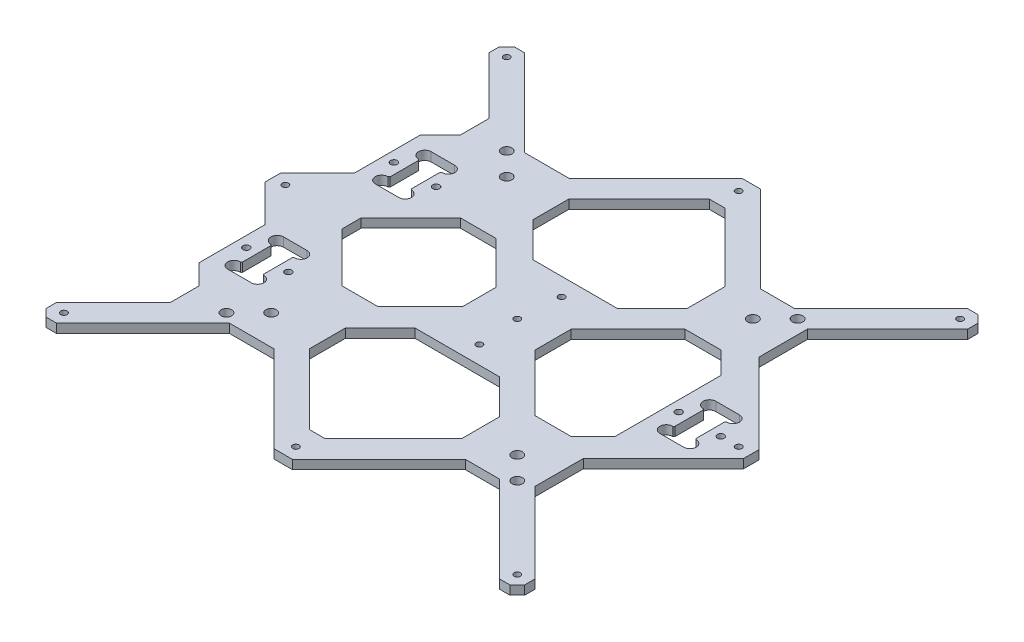
SolidWorks part; units mm, degrees
material "6063-O, Extruded Rod (SS)"
ref_plane "Front Plane" through (0, 0, 0) normal (0, 0, 1) x (1, 0, 0)
ref_plane "Top Plane" through (0, 0, 0) normal (0, 1, 0) x (1, 0, 0)
ref_plane "Right Plane" through (0, 0, 0) normal (1, 0, 0) x (0, 0, -1)
sketch "Sketch2" plane through (0, 0, 0) normal (0, 1, 0) x (1, 0, 0)
  line L0 (162, 177.023) -> (141.977, 157)
  line L1 (141.977, 157) -> (125, 157)
  line L2 (125, 157) -> (101.5, 180.5)
  line L3 (101.5, 189.5) -> (125, 213)
  line L4 (125, 213) -> (141.977, 213)
  line L5 (141.977, 213) -> (162, 192.977)
  line L6 (251.5, 210.0147) -> (240.9853, 220.5294)
  line L7 (240.9853, 220.5294) -> (224.0147, 220.5294)
  line L8 (224.0147, 220.5294) -> (197, 193.5147)
  line L9 (197, 176.4853) -> (224.0147, 149.4706)
  line L10 (224.0147, 149.4706) -> (240.9853, 149.4706)
  line L11 (240.9853, 149.4706) -> (251.5, 159.9853)
  line L12 (184.4001, 296) -> (225.4001, 255)
  line L13 (225.4001, 255) -> (241.5147, 255)
  line L14 (241.5147, 255) -> (282.5147, 296)
  line L15 (282.5147, 296) -> (287.4852, 296)
  line L16 (287.4852, 296) -> (291, 292.4852)
  line L17 (291, 292.4852) -> (291, 287.5147)
  line L18 (291, 287.5147) -> (253, 249.5147)
  line L19 (253, 249.5147) -> (253, 226.667)
  line L20 (253, 226.667) -> (291, 188.667)
  line L21 (291, 188.667) -> (291, 181.333)
  line L22 (291, 181.333) -> (253, 143.333)
  line L23 (253, 143.333) -> (253, 120.4853)
  line L24 (253, 120.4853) -> (291, 82.4853)
  line L25 (291, 82.4853) -> (291, 77.5148)
  line L26 (291, 77.5148) -> (287.4852, 74)
  line L27 (287.4852, 74) -> (282.5147, 74)
  line L28 (282.5147, 74) -> (241.5147, 115)
  line L29 (241.5147, 115) -> (225.4001, 115)
  line L30 (225.4001, 115) -> (184.4001, 74)
  line L31 (184.4001, 74) -> (175.5999, 74)
  line L32 (175.5999, 74) -> (134.5999, 115)
  line L33 (134.5999, 115) -> (113.4853, 115)
  line L34 (113.4853, 115) -> (72.4853, 74)
  line L35 (72.4853, 74) -> (67.5148, 74)
  line L36 (67.5148, 74) -> (64, 77.5148)
  line L37 (64, 77.5148) -> (64, 82.4853)
  line L38 (64, 82.4853) -> (91, 109.4853)
  line L39 (91, 109.4853) -> (91, 123)
  line L40 (91, 123) -> (81.5, 132.5)
  line L41 (81.5, 132.5) -> (81.5, 163.7609)
  line L42 (81.5, 163.7609) -> (64, 181.2609)
  line L43 (64, 188.7391) -> (81.5, 206.2391)
  line L44 (81.5, 206.2391) -> (81.5, 237.5)
  line L45 (81.5, 237.5) -> (91, 247)
  line L46 (91, 247) -> (91, 260.5147)
  line L47 (91, 260.5147) -> (64, 287.5147)
  line L48 (64, 287.5147) -> (64, 292.4852)
  line L49 (64, 292.4852) -> (67.5148, 296)
  line L50 (67.5148, 296) -> (72.4853, 296)
  line L51 (72.4853, 296) -> (113.4853, 255)
  line L52 (113.4853, 255) -> (134.5999, 255)
  line L53 (134.5999, 255) -> (175.5999, 296)
  line L54 (175.5999, 296) -> (184.4001, 296)
  line L55 (143, 246.4158) -> (143, 229.5663)
  line L56 (143, 229.5663) -> (159.5663, 213)
  line L57 (159.5663, 213) -> (199.5147, 213)
  line L58 (199.5147, 213) -> (216, 229.4853)
  line L59 (216, 229.4853) -> (216, 247.4296)
  line L60 (216, 247.4296) -> (183.6826, 279.747)
  line L61 (183.6826, 279.747) -> (176.3174, 279.7332)
  line L62 (176.3174, 279.7332) -> (143, 246.4158)
  line L63 (143, 123.5842) -> (143, 140.4337)
  line L64 (143, 140.4337) -> (159.5663, 157)
  line L65 (159.5663, 157) -> (199.5147, 157)
  line L66 (199.5147, 157) -> (216, 140.5147)
  line L67 (216, 140.5147) -> (216, 122.5704)
  line L68 (216, 122.5704) -> (183.6826, 90.253)
  line L69 (183.6826, 90.253) -> (176.3174, 90.2668)
  line L70 (176.3174, 90.2668) -> (143, 123.5842)
  line L71 (101.5, 226.75) -> (101.5, 213.25)
  line L72 (271.5, 191.75) -> (271.5, 178.25)
  line L73 (101.5, 156.75) -> (101.5, 143.25)
  line L74 (91.5, 226.75) -> (91.5, 213.25)
  line L75 (261.5, 191.75) -> (261.5, 178.25)
  line L76 (91.5, 156.75) -> (91.5, 143.25)
  line L77 (93.6792, 358.4107) -> (93.6792, 347.8262)
  line L78 (93.6792, 347.8262) -> (93.9406, 345.7354)
  line L79 (93.9406, 345.7354) -> (94.4633, 344.2327)
  line L80 (94.4633, 344.2327) -> (95.182, 343.1873)
  line L81 (95.182, 343.1873) -> (96.1846, 341.9648)
  line L82 (96.1846, 341.9648) -> (97.8105, 341.4329)
  line L83 (97.8105, 341.4329) -> (99.6248, 341.0966)
  line L84 (99.6248, 341.0966) -> (101.977, 341.3579)
  line L85 (101.977, 341.3579) -> (104.0024, 342.4033)
  line L86 (104.0024, 342.4033) -> (105.1131, 344.2327)
  line L87 (105.1131, 344.2327) -> (105.5705, 346.7155)
  line L88 (105.5705, 346.7155) -> (105.5705, 349.1983)
  line L89 (105.5705, 349.1983) -> (105.5705, 358.4107)
  line L90 (79.8932, 349.3289) -> (80.0892, 349.3289)
  line L91 (80.0892, 349.3289) -> (81.0039, 348.8063)
  line L92 (81.0039, 348.8063) -> (82.0493, 347.4342)
  line L93 (82.0493, 347.4342) -> (86.4922, 341.0966)
  line L94 (73.5556, 341.1619) -> (73.5556, 358.4107)
  line L95 (73.5556, 358.4107) -> (80.6119, 358.4107)
  line L96 (80.6119, 358.4107) -> (82.768, 357.7574)
  line L97 (82.768, 357.7574) -> (83.8134, 356.7773)
  line L98 (83.8134, 356.7773) -> (84.5321, 355.4706)
  line L99 (84.5321, 355.4706) -> (84.8588, 353.7065)
  line L100 (84.8588, 353.7065) -> (84.5321, 352.0078)
  line L101 (84.5321, 352.0078) -> (83.6827, 350.5703)
  line L102 (83.6827, 350.5703) -> (82.5067, 349.8517)
  line L103 (82.5067, 349.8517) -> (81.3306, 349.525)
  line L104 (81.3306, 349.525) -> (79.8932, 349.3289)
  line L105 (79.8932, 349.3289) -> (78.1291, 349.3289)
  line L106 (78.1291, 349.3289) -> (73.5556, 349.3289)
  line L107 (113.0897, 345.4442) -> (114.2004, 343.4842)
  line L108 (114.2004, 343.4842) -> (116.6178, 341.8507)
  line L109 (116.6178, 341.8507) -> (118.9699, 341.1974)
  line L110 (118.9699, 341.1974) -> (122.4328, 341.7201)
  line L111 (122.4328, 341.7201) -> (124.0662, 343.0268)
  line L112 (124.0662, 343.0268) -> (125.2422, 345.1176)
  line L113 (125.2422, 345.1176) -> (125.2422, 346.359)
  line L114 (125.2422, 346.359) -> (124.9156, 347.4697)
  line L115 (124.9156, 347.4697) -> (123.7395, 348.7764)
  line L116 (123.7395, 348.7764) -> (122.5635, 349.2991)
  line L117 (122.5635, 349.2991) -> (116.7485, 351.0632)
  line L118 (116.7485, 351.0632) -> (115.0497, 352.1739)
  line L119 (115.0497, 352.1739) -> (114.0044, 353.4153)
  line L120 (114.0044, 353.4153) -> (113.8737, 354.5914)
  line L121 (113.8737, 354.5914) -> (114.135, 356.3554)
  line L122 (114.135, 356.3554) -> (115.3764, 357.6622)
  line L123 (115.3764, 357.6622) -> (117.4672, 358.4462)
  line L124 (117.4672, 358.4462) -> (120.0807, 358.5769)
  line L125 (120.0807, 358.5769) -> (122.8248, 357.8582)
  line L126 (122.8248, 357.8582) -> (123.9355, 356.8128)
  line L127 (123.9355, 356.8128) -> (124.3929, 355.5714)
  line L128 (130.9954, 341.0312) -> (137.9864, 358.5414)
  line L129 (137.9864, 358.5414) -> (139.0972, 358.5414)
  line L130 (139.0972, 358.5414) -> (145.9575, 341.0312)
  line L131 (143.9343, 346.1951) -> (133.0803, 346.1927)
  line L132 (55, 341.1619) -> (55, 358.4107)
  line L133 (55, 358.4107) -> (62.0563, 358.4107)
  line L134 (62.0563, 358.4107) -> (64.2125, 357.7574)
  line L135 (64.2125, 357.7574) -> (65.2578, 356.7773)
  line L136 (65.2578, 356.7773) -> (65.9765, 355.4706)
  line L137 (65.9765, 355.4706) -> (66.3032, 353.7065)
  line L138 (66.3032, 353.7065) -> (65.9765, 352.0078)
  line L139 (65.9765, 352.0078) -> (65.1272, 350.5703)
  line L140 (65.1272, 350.5703) -> (63.9511, 349.8517)
  line L141 (63.9511, 349.8517) -> (62.7751, 349.525)
  line L142 (62.7751, 349.525) -> (61.3376, 349.3289)
  line L143 (61.3376, 349.3289) -> (59.5735, 349.3289)
  line L144 (59.5735, 349.3289) -> (55, 349.3289)
  line L145 (251.5, 210.0147) -> (251.5, 159.9853)
  line L146 (197, 193.5147) -> (197, 176.4853)
  line L147 (64, 188.7391) -> (64, 181.2609)
  line L148 (101.5, 189.5) -> (101.5, 180.5)
  line L149 (162, 192.977) -> (162, 177.023)
  line L150 (102.1, 142.75) -> (102, 142.75)
  line L151 (272.1, 177.75) -> (272, 177.75)
  line L152 (102.1, 212.75) -> (102, 212.75)
  line L153 (90.9, 142.75) -> (91, 142.75)
  line L154 (260.9, 177.75) -> (261, 177.75)
  line L155 (90.9, 212.75) -> (91, 212.75)
  line L156 (102, 142.75) -> (101.5, 143.25)
  line L157 (272, 177.75) -> (271.5, 178.25)
  line L158 (102, 212.75) -> (101.5, 213.25)
  line L159 (91, 142.75) -> (91.5, 143.25)
  line L160 (261, 177.75) -> (261.5, 178.25)
  line L161 (91, 212.75) -> (91.5, 213.25)
  line L162 (102.1, 157.25) -> (102, 157.25)
  line L163 (272.1, 192.25) -> (272, 192.25)
  line L164 (102.1, 227.25) -> (102, 227.25)
  line L165 (90.9, 157.25) -> (91, 157.25)
  line L166 (260.9, 192.25) -> (261, 192.25)
  line L167 (90.9, 227.25) -> (91, 227.25)
  line L168 (101.5, 156.75) -> (102, 157.25)
  line L169 (271.5, 191.75) -> (272, 192.25)
  line L170 (101.5, 226.75) -> (102, 227.25)
  line L171 (91.5, 156.75) -> (91, 157.25)
  line L172 (261.5, 191.75) -> (261, 192.25)
  line L173 (91.5, 226.75) -> (91, 227.25)
  line L174 (90.9, 163.25) -> (102.1, 163.25)
  line L175 (260.9, 198.25) -> (272.1, 198.25)
  line L176 (90.9, 233.25) -> (102.1, 233.25)
  line L177 (90.9, 136.75) -> (102.1, 136.75)
  line L178 (260.9, 171.75) -> (272.1, 171.75)
  line L179 (90.9, 206.75) -> (102.1, 206.75)
  arc A0 (102.1, 206.75) -> (102.1, 212.75) centre (102.1, 209.75) ccw
  arc A1 (272.1, 171.75) -> (272.1, 177.75) centre (272.1, 174.75) ccw
  arc A2 (102.1, 136.75) -> (102.1, 142.75) centre (102.1, 139.75) ccw
  arc A3 (90.9, 142.75) -> (90.9, 136.75) centre (90.9, 139.75) ccw
  arc A4 (90.9, 212.75) -> (90.9, 206.75) centre (90.9, 209.75) ccw
  arc A5 (260.9, 177.75) -> (260.9, 171.75) centre (260.9, 174.75) ccw
  arc A6 (102.1, 157.25) -> (102.1, 163.25) centre (102.1, 160.25) ccw
  arc A7 (102.1, 227.25) -> (102.1, 233.25) centre (102.1, 230.25) ccw
  arc A8 (272.1, 192.25) -> (272.1, 198.25) centre (272.1, 195.25) ccw
  arc A9 (90.9, 163.25) -> (90.9, 157.25) centre (90.9, 160.25) ccw
  arc A10 (260.9, 198.25) -> (260.9, 192.25) centre (260.9, 195.25) ccw
  arc A11 (90.9, 233.25) -> (90.9, 227.25) centre (90.9, 230.25) ccw
  circle A12 centre (318.6, 4.9) radius 2.55
  circle A13 centre (318.6, 28.1) radius 2.55
  circle A14 centre (295.4, 28.1) radius 2.55
  circle A15 centre (295.4, 4.9) radius 2.55
  circle A16 centre (281.6, 4.9) radius 2.55
  circle A17 centre (258.4, 4.9) radius 2.55
  circle A18 centre (258.4, 28.1) radius 2.55
  circle A19 centre (281.6, 28.1) radius 2.55
  circle A20 centre (111.6, 4.9) radius 2.55
  circle A21 centre (111.6, 28.1) radius 2.55
  circle A22 centre (88.4, 28.1) radius 2.55
  circle A23 centre (88.4, 4.9) radius 2.55
  circle A24 centre (74.6, 4.9) radius 2.55
  circle A25 centre (74.6, 28.1) radius 2.55
  circle A26 centre (51.4, 28.1) radius 2.55
  circle A27 centre (51.4, 4.9) radius 2.55
  circle A28 centre (360, 39.8) radius 1.5
  circle A29 centre (10, 39.8) radius 1.5
  circle A30 centre (340, 359.8) radius 1.5
  circle A31 centre (30, 39.8) radius 1.5
  circle A32 centre (42.9, 67.8) radius 1.5
  circle A33 centre (340, 39.8) radius 1.5
  circle A34 centre (10, 359.8) radius 1.5
  circle A35 centre (350, 19.8) radius 1.5
  circle A36 centre (47, 99.8) radius 1.5
  circle A37 centre (3.7, 181.1) radius 1.5
  circle A38 centre (20, 19.8) radius 1.5
  circle A39 centre (4.9, 67.8) radius 1.5
  circle A40 centre (360, 359.8) radius 1.5
  circle A41 centre (42.9, 161.8) radius 1.5
  circle A42 centre (3.7, 99.8) radius 1.5
  circle A43 centre (30, 359.8) radius 1.5
  circle A44 centre (47, 174.7) radius 1.5
  circle A45 centre (4.9, 161.8) radius 1.5
  circle A46 centre (46.5, 269.3) radius 1.5
  circle A47 centre (15, 247.8) radius 1.5
  circle A48 centre (3.5, 269.3) radius 1.5
  circle A49 centre (15, 290.8) radius 1.5
  circle A50 centre (180, 80) radius 1.5
  circle A51 centre (180, 290) radius 1.5
  circle A52 centre (285, 80) radius 1.5
  circle A53 centre (70, 290) radius 1.5
  circle A54 centre (285, 290) radius 1.5
  circle A55 centre (70, 185) radius 1.5
  circle A56 centre (180, 185) radius 1.5
  circle A57 centre (285, 185) radius 1.5
  circle A58 centre (256.5, 185) radius 1.6
  circle A59 centre (276.5, 185) radius 1.6
  circle A60 centre (106.5, 220) radius 1.6
  circle A61 centre (106.5, 150) radius 1.6
  circle A62 centre (86.5, 220) radius 1.6
  circle A63 centre (86.5, 150) radius 1.6
  circle A64 centre (70, 80) radius 1.5
  circle A65 centre (181.5, 165.5) radius 1.5
  circle A66 centre (181.5, 204.5) radius 1.5
  circle A67 centre (40, 7) radius 1.6
  circle A68 centre (331, 7) radius 1.6
  circle A69 centre (343, 7) radius 1.6
  circle A70 centre (120, 13) radius 1.6
  circle A71 centre (120, 4) radius 1.6
  circle A72 centre (230, 13) radius 1.6
  circle A73 centre (230, 4) radius 1.6
  circle A74 centre (333.4, 205) radius 2.1
  circle A75 centre (333.4, 88) radius 2.1
  circle A76 centre (26, 7) radius 1.6
  circle A77 centre (153, 13) radius 1.6
  circle A78 centre (153, 4) radius 1.6
  spline S0 degree 2 poles (5, 370) (2.5, 367.5) (0, 365) knots 1472.868668 1472.868668 1472.868668 1479.939736 1479.939736 1479.939736
  spline S1 degree 2 poles (365, 370) (185, 370) (5, 370) knots 1112.868668 1112.868668 1112.868668 1472.868668 1472.868668 1472.868668
  spline S2 degree 2 poles (370, 365) (367.5, 367.5) (365, 370) knots 1105.7976 1105.7976 1105.7976 1112.868668 1112.868668 1112.868668
  spline S3 degree 2 poles (370, 5) (370, 185) (370, 365) knots 745.7976 745.7976 745.7976 1105.7976 1105.7976 1105.7976
  spline S4 degree 2 poles (365, 0) (367.5, 2.5) (370, 5) knots 738.726533 738.726533 738.726533 745.7976 745.7976 745.7976
  spline S5 degree 2 poles (345, 0) (355, 0) (365, 0) knots 718.726533 718.726533 718.726533 738.726533 738.726533 738.726533
  spline S6 degree 2 poles (341, 4) (343, 2) (345, 0) knots 710.241251 710.241251 710.241251 718.726533 718.726533 718.726533
  spline S7 degree 2 poles (333, 4) (337, 4) (341, 4) knots 704.241251 704.241251 704.241251 710.241251 710.241251 710.241251
  spline S8 degree 2 poles (329, 0) (331, 2) (333, 4) knots 698.584397 698.584397 698.584397 704.241251 704.241251 704.241251
  spline S9 degree 2 poles (151, 0) (240, 0) (329, 0) knots 507.584397 507.584397 507.584397 698.584397 698.584397 698.584397
  spline S10 degree 2 poles (146, 5) (148.5, 2.5) (151, 0) knots 501.927543 501.927543 501.927543 507.584397 507.584397 507.584397
  spline S11 degree 2 poles (127, 5) (136.5, 5) (146, 5) knots 487.927543 487.927543 487.927543 501.927543 501.927543 501.927543
  spline S12 degree 2 poles (122, 0) (124.5, 2.5) (127, 5) knots 482.270688 482.270688 482.270688 487.927543 487.927543 487.927543
  spline S13 degree 2 poles (41, 0) (81.5, 0) (122, 0) knots 407.270688 407.270688 407.270688 482.270688 482.270688 482.270688
  spline S14 degree 2 poles (37, 4) (39, 2) (41, 0) knots 401.613834 401.613834 401.613834 407.270688 407.270688 407.270688
  spline S15 degree 2 poles (29, 4) (33, 4) (37, 4) knots 395.613834 395.613834 395.613834 401.613834 401.613834 401.613834
  spline S16 degree 2 poles (25, 0) (27, 2) (29, 4) knots 387.128553 387.128553 387.128553 395.613834 395.613834 395.613834
  spline S17 degree 2 poles (5, 0) (15, 0) (25, 0) knots 367.128553 367.128553 367.128553 387.128553 387.128553 387.128553
  spline S18 degree 2 poles (0, 5) (2.5, 2.5) (5, 0) knots 360.191742 360.191742 360.191742 367.128553 367.128553 367.128553
  spline S19 degree 2 poles (0, 365) (0, 185) (0, 5) knots 0 0 0 360.191742 360.191742 360.191742
  spline S20 degree 2 poles (93, 31.5) (100, 31.5) (107, 31.5) knots 1110.421356 1110.421356 1110.421356 1117.046356 1117.046356 1117.046356
  spline S21 degree 2 poles (88, 36.5) (90.5, 34) (93, 31.5) knots 1103.350288 1103.350288 1103.350288 1110.421356 1110.421356 1110.421356
  spline S22 degree 2 poles (83, 36.5) (85.5, 36.5) (88, 36.5) knots 1098.350288 1098.350288 1098.350288 1103.350288 1103.350288 1103.350288
  spline S23 degree 2 poles (73, 46.5) (78, 41.5) (83, 36.5) knots 1084.208153 1084.208153 1084.208153 1098.350288 1098.350288 1098.350288
  spline S24 degree 2 poles (55, 46.5) (64, 46.5) (73, 46.5) knots 1066.208153 1066.208153 1066.208153 1084.208153 1084.208153 1084.208153
  spline S25 degree 2 poles (50, 51.5) (52.5, 49) (55, 46.5) knots 1059.137085 1059.137085 1059.137085 1066.208153 1066.208153 1066.208153
  spline S26 degree 2 poles (50, 325) (50, 188.25) (50, 51.5) knots 787.637085 787.637085 787.637085 1059.137085 1059.137085 1059.137085
  spline S27 degree 2 poles (55, 330) (52.5, 327.5) (50, 325) knots 780.566017 780.566017 780.566017 787.637085 787.637085 787.637085
  spline S28 degree 2 poles (315, 330) (185, 330) (55, 330) knots 520.566017 520.566017 520.566017 780.566017 780.566017 780.566017
  spline S29 degree 2 poles (320, 325) (317.5, 327.5) (315, 330) knots 513.494949 513.494949 513.494949 520.566017 520.566017 520.566017
  spline S30 degree 2 poles (320, 51.5) (320, 188.25) (320, 325) knots 241.994949 241.994949 241.994949 513.494949 513.494949 513.494949
  spline S31 degree 2 poles (315, 46.5) (317.5, 49) (320, 51.5) knots 234.923882 234.923882 234.923882 241.994949 241.994949 241.994949
  spline S32 degree 2 poles (297, 46.5) (306, 46.5) (315, 46.5) knots 216.923882 216.923882 216.923882 234.923882 234.923882 234.923882
  spline S33 degree 2 poles (287, 36.5) (292, 41.5) (297, 46.5) knots 202.781746 202.781746 202.781746 216.923882 216.923882 216.923882
  spline S34 degree 2 poles (282, 36.5) (284.5, 36.5) (287, 36.5) knots 197.781746 197.781746 197.781746 202.781746 202.781746 202.781746
  spline S35 degree 2 poles (277, 31.5) (279.5, 34) (282, 36.5) knots 190.710678 190.710678 190.710678 197.781746 197.781746 197.781746
  spline S36 degree 2 poles (263, 31.5) (264, 31.5) (265, 31.5) (270, 31.5) (275, 31.5) (276, 31.5) (277, 31.5) knots 176.710678 176.710678 176.710678 178.710678 178.710678 188.710678 188.710678 190.710678 190.710678 190.710678
  spline S37 degree 2 poles (258, 36.5) (260.5, 34) (263, 31.5) knots 169.63961 169.63961 169.63961 176.710678 176.710678 176.710678
  spline S38 degree 2 poles (210, 36.5) (211.75, 36.5) (213.5, 36.5) (235.75, 36.5) (258, 36.5) knots 121.63961 121.63961 121.63961 125.13961 125.13961 169.63961 169.63961 169.63961
  spline S39 degree 2 poles (190, 16.5) (200, 26.5) (210, 36.5) knots 93.355339 93.355339 93.355339 121.63961 121.63961 121.63961
  spline S40 degree 2 poles (180, 16.5) (185, 16.5) (190, 16.5) knots 83.355339 83.355339 83.355339 93.355339 93.355339 93.355339
  spline S41 degree 2 poles (160, 36.5) (170, 26.5) (180, 16.5) knots 55.071068 55.071068 55.071068 83.355339 83.355339 83.355339
  spline S42 degree 2 poles (112, 36.5) (134.25, 36.5) (156.5, 36.5) (158.25, 36.5) (160, 36.5) knots 7.071068 7.071068 7.071068 51.571068 51.571068 55.071068 55.071068 55.071068
  spline S43 degree 2 poles (107, 31.5) (109.5, 34) (112, 36.5) knots 0 0 0 7.071068 7.071068 7.071068
extrude "Boss-Extrude2" add sketch "Sketch2" along normal blind 4.25 contours L43 L147 L42 L41 L40 L39 L38 L37 L36 L35 L34 L33 L32 L31 L30 L29 L28 L27 L26 L25 L24 L23 L22 L21 L20 L19 L18 L17 L16 L15 L14 L13 L12 L54 L53 L52 L51 L50 L49 L48 L47 L46 L45 L44 A66 A65 A64 region at (170.1997, 0, -185)
sketch "Sketch3" plane through (0, 4.25, 0) normal (0, 1, 0) x (1, 0, 0)
  line L0 (181.5, 203) -> (181.5, 206) construction
  line L1 (180, 204.5) -> (183, 204.5) construction
  line L2 (180, 165.5) -> (183, 165.5) construction
  circle A0 centre (181.5, 204.5) radius 1.5 construction
  circle A1 centre (181.5, 204.5) radius 1.5 construction
  circle A2 centre (181.5, 165.5) radius 1.5 construction
ref_plane "Plane1" through (181.5, 0, 0) normal (1, 0, 0) x (0, 0, -1)
ref_plane "Plane2" through (0, 0, -165.5) normal (0, 0, 1) x (1, 0, 0)
ref_plane "Plane3" through (0, 0, -204.5) normal (0, 0, -1) x (-1, 0, 0)
sketch "Sketch4" plane through (0, 4.25, 0) normal (0, 1, 0) x (1, 0, 0)
  line L0 (91, 260.5147) -> (118.0833, 233.4314) construction
  line L2 (241.5147, 255) -> (228.4314, 241.9167) construction
  line L4 (241.5147, 115) -> (228.4314, 128.0833) construction
  line L7 (113.4853, 115) -> (72.4853, 74) construction
  line L8 (126.5686, 128.0833) -> (118.0833, 136.5686) construction
  line L9 (118.0833, 136.5686) -> (91, 109.4853) construction
  line L10 (64, 82.4853) -> (91, 109.4853) construction
  line L11 (67.5148, 74) -> (64, 77.5148) construction
  line L12 (126.5686, 128.0833) -> (113.4853, 115) construction
  line L13 (122.326, 132.326) -> (65.7574, 75.7574) construction
  line L14 (228.4314, 128.0833) -> (236.9167, 136.5686) construction
  line L15 (236.9167, 136.5686) -> (253, 120.4853) construction
  line L16 (282.5147, 74) -> (241.5147, 115) construction
  line L17 (291, 77.5148) -> (287.4852, 74) construction
  line L18 (118.0833, 233.4314) -> (126.5686, 241.9167) construction
  line L19 (126.5686, 241.9167) -> (113.4853, 255) construction
  line L20 (91, 260.5147) -> (64, 287.5147) construction
  line L21 (64, 292.4852) -> (67.5148, 296) construction
  line L22 (228.4314, 241.9167) -> (236.9167, 233.4314) construction
  line L23 (236.9167, 233.4314) -> (253, 249.5147) construction
  line L24 (291, 287.5147) -> (253, 249.5147) construction
  line L25 (287.4852, 296) -> (291, 292.4852) construction
  line L26 (122.326, 237.674) -> (65.7574, 294.2426) construction
  line L27 (232.674, 237.674) -> (289.2426, 294.2426) construction
  line L28 (232.674, 132.326) -> (289.2426, 75.7574) construction
  circle A4 centre (119.144, 129.144) radius 2.5
  circle A5 centre (108.5374, 118.5374) radius 2.5
  circle A6 centre (108.5374, 251.4626) radius 2.5
  circle A7 centre (119.144, 240.856) radius 2.5
  circle A8 centre (235.856, 240.856) radius 2.5
  circle A9 centre (246.4626, 251.4626) radius 2.5
  circle A10 centre (235.856, 129.144) radius 2.5
  circle A11 centre (246.4626, 118.5374) radius 2.5
  dimension "D4" = 5
  dimension "D7" = 5
  dimension "D8" = 15
  dimension "D10" = 5
  dimension "D11" = 5
  dimension "D14" = 5
  dimension "D15" = 5
  dimension "D18" = 5
  dimension "D19" = 5
  dimension "D2" = 80
  dimension "D3" = 80
  dimension "D5" = 80
  dimension "D6" = 4.5
  dimension "D9" = 80
  dimension "D12" = 15
  dimension "D13" = 4.5
  dimension "D16" = 15
  dimension "D17" = 4.5
  dimension "D20" = 15
  dimension "D21" = 4.5
extrude "Holes-to-drill" cut sketch "Sketch4" against normal through all
